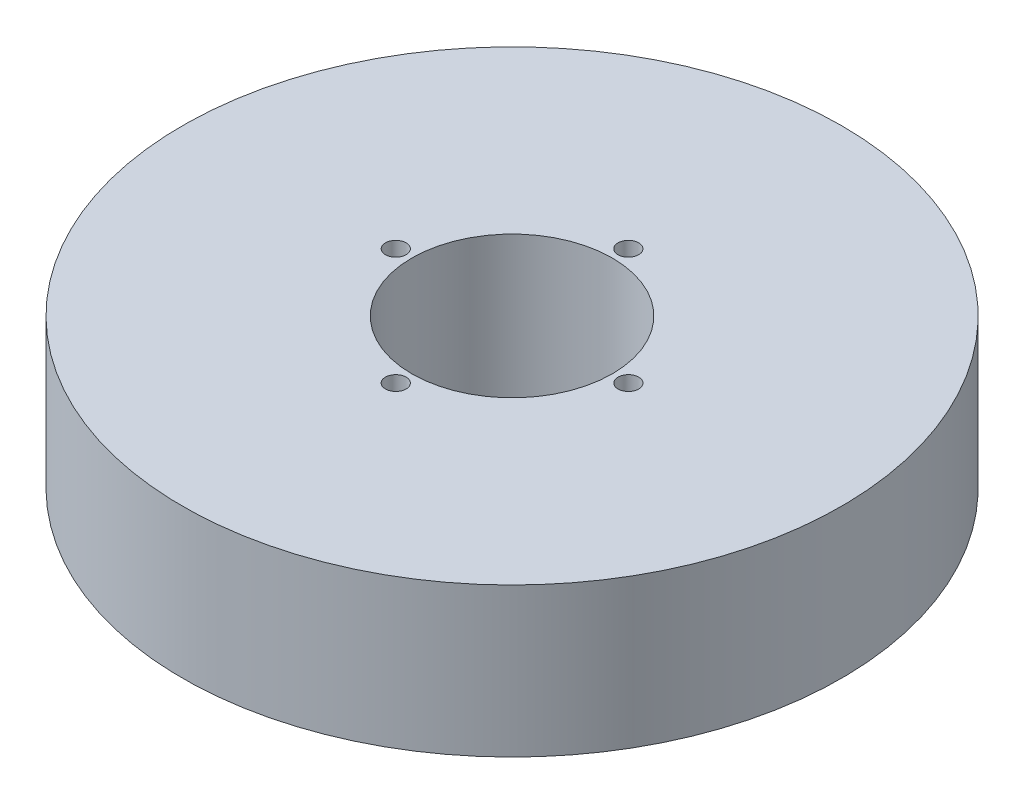
SolidWorks part; units mm, degrees
ref_plane "Front Plane" through (0, 0, 0) normal (0, 0, 1) x (1, 0, 0)
ref_plane "Top Plane" through (0, 0, 0) normal (0, 1, 0) x (1, 0, 0)
ref_plane "Right Plane" through (0, 0, 0) normal (1, 0, 0) x (0, 0, -1)
sketch "Sketch1" plane through (0, 0, 0) normal (0, 1, 0) x (1, 0, 0)
  circle A0 centre (0, 0) radius 57.5
  dimension "FLANGE_OD" = 115
extrude "Boss-Extrude1" add sketch "Sketch1" along normal blind 26
sketch "Sketch2" plane through (0, 0, 0) normal (0, 1, 0) x (1, 0, 0)
  circle A0 centre (0, 0) radius 17.5
  dimension "BORE_D" = 35
extrude "Cut-Extrude1" cut sketch "Sketch2" along normal through all
sketch "Sketch3" plane through (0, 26, 0) normal (0, 1, 0) x (1, 0, 0)
  circle A0 centre (0, 0) radius 20.2895 construction
  circle A1 centre (-20.2895, 0) radius 1.8036
  dimension "BOLT_D" = 3.6072
  dimension "BOLT_PCD" = 40.579
extrude "Cut-Extrude2" cut sketch "Sketch3" against normal blind 18.4784
pattern_circular "CirPattern1" count 4 over 360 about axis through (0, 0, 0) along (0, 1, 0) of "Cut-Extrude2"
